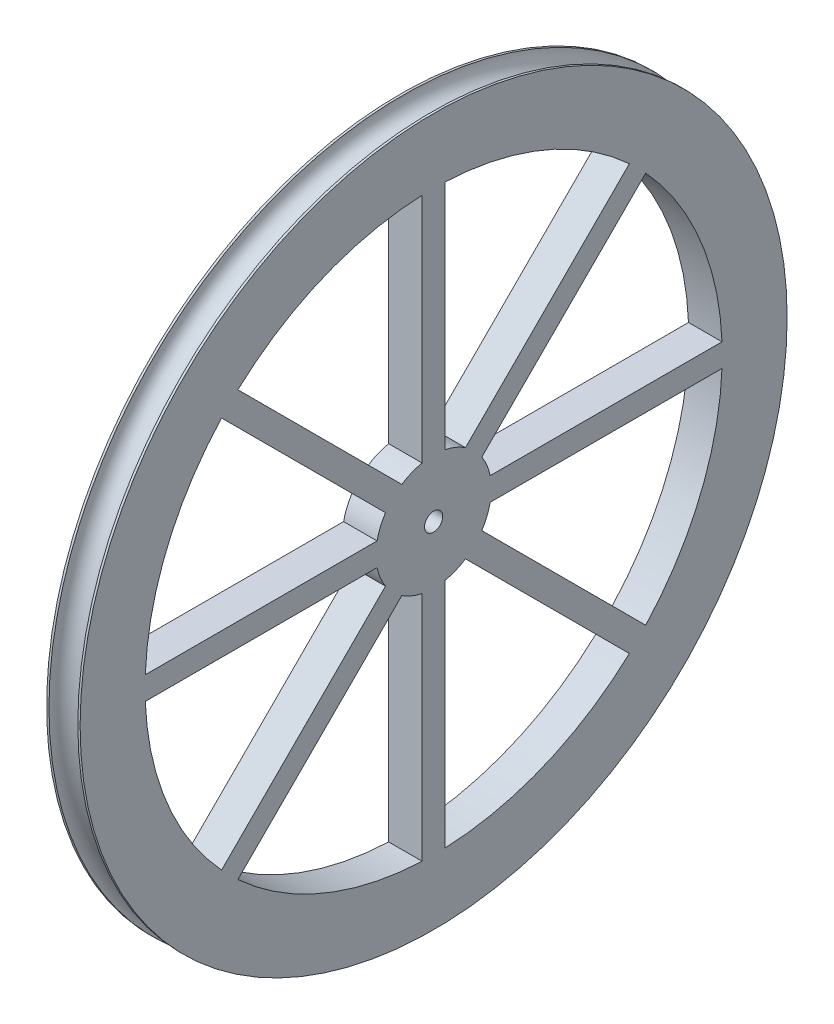
SolidWorks part; units mm, degrees
ref_plane "Front Plane" through (0, 0, 0) normal (0, 0, 1) x (1, 0, 0)
ref_plane "Top Plane" through (0, 0, 0) normal (0, 1, 0) x (1, 0, 0)
ref_plane "Right Plane" through (0, 0, 0) normal (1, 0, 0) x (0, 0, -1)
sketch "Sketch1" plane through (0, 0, 0) normal (1, 0, 0) x (0, 0, -1)
  circle A0 centre (0, 0) radius 38.8938
  dimension "D1" = 77.7875
extrude "Boss-Extrude1" add sketch "Sketch1" along normal blind 3.683
sketch "Sketch10" plane through (0, 0, 0) normal (0, 0, 1) x (1, 0, 0)
  line L0 (3.683, 38.8938) -> (0, 38.8938) construction
  line L1 (-1.0162, 0) -> (5.466, 0) construction
  line L2 (55, 0) -> (-55, 0) construction
  circle A0 centre (1.8415, 38.8938) radius 1.5875
  dimension "D1" = 3.175
revolve "Cut-Revolve1" cut sketch "Sketch10" angle 360 about L1
sketch "Sketch11" plane through (3.683, 0, 0) normal (1, 0, 0) x (0, 0, -1)
  line L2 (0, -50.6508) -> (0, 43.6326) construction
  line L3 (-53.144, 0) -> (6.35, 0) construction
  line L4 (-1.27, 31.7246) -> (-1.27, 6.2217)
  line L5 (1.27, 31.7246) -> (1.27, 6.2217)
  line L6 (21.5346, 23.3307) -> (3.5014, 5.2974)
  line L7 (23.3307, 21.5346) -> (5.2974, 3.5014)
  line L8 (31.7246, 1.27) -> (6.2217, 1.27)
  line L9 (31.7246, -1.27) -> (6.2217, -1.27)
  line L10 (23.3307, -21.5346) -> (5.2974, -3.5014)
  line L11 (21.5346, -23.3307) -> (3.5014, -5.2974)
  line L12 (1.27, -31.7246) -> (1.27, -6.2217)
  line L13 (-1.27, -31.7246) -> (-1.27, -6.2217)
  line L14 (-21.5346, -23.3307) -> (-3.5014, -5.2974)
  line L15 (-23.3307, -21.5346) -> (-5.2974, -3.5014)
  line L16 (-31.7246, -1.27) -> (-6.2217, -1.27)
  line L17 (-31.7246, 1.27) -> (-6.2217, 1.27)
  line L18 (-23.3307, 21.5346) -> (-5.2974, 3.5014)
  line L19 (-21.5346, 23.3307) -> (-3.5014, 5.2974)
  arc A2 (5.2974, -3.5014) -> (6.2217, -1.27) centre (0, 0) ccw
  arc A3 (-23.3307, 21.5346) -> (-31.7246, 1.27) centre (0, 0) ccw
  arc A4 (21.5346, 23.3307) -> (1.27, 31.7246) centre (0, 0) ccw
  arc A5 (-1.27, 31.7246) -> (-21.5346, 23.3307) centre (0, 0) ccw
  arc A6 (31.7246, 1.27) -> (23.3307, 21.5346) centre (0, 0) ccw
  arc A7 (23.3307, -21.5346) -> (31.7246, -1.27) centre (0, 0) ccw
  arc A8 (1.27, -31.7246) -> (21.5346, -23.3307) centre (0, 0) ccw
  arc A9 (-21.5346, -23.3307) -> (-1.27, -31.7246) centre (0, 0) ccw
  arc A10 (-31.7246, -1.27) -> (-23.3307, -21.5346) centre (0, 0) ccw
  arc A11 (1.27, -6.2217) -> (3.5014, -5.2974) centre (0, 0) ccw
  arc A12 (-3.5014, -5.2974) -> (-1.27, -6.2217) centre (0, 0) ccw
  arc A13 (-6.2217, -1.27) -> (-5.2974, -3.5014) centre (0, 0) ccw
  arc A14 (-5.2974, 3.5014) -> (-6.2217, 1.27) centre (0, 0) ccw
  arc A15 (-1.27, 6.2217) -> (-3.5014, 5.2974) centre (0, 0) ccw
  arc A16 (3.5014, 5.2974) -> (1.27, 6.2217) centre (0, 0) ccw
  arc A17 (6.2217, 1.27) -> (5.2974, 3.5014) centre (0, 0) ccw
  point P17 (0, 0)
  point P18 (-21.5659, 23.3018)
  point P43 (0, 0)
  point P44 (-3.4966, 5.3006)
  dimension "D1" = 12.7
  dimension "D2" = 63.5
  dimension "D3" = 2.54
  dimension "D4" = 1.27
  dimension "D5" = 8
extrude "Cut-Extrude3" cut sketch "Sketch11" against normal through all
sketch "Sketch12" plane through (3.683, 0, 0) normal (1, 0, 0) x (0, 0, -1)
  circle A0 centre (0, 0) radius 1
  dimension "D1" = 2
extrude "Cut-Extrude4" cut sketch "Sketch12" against normal through all
